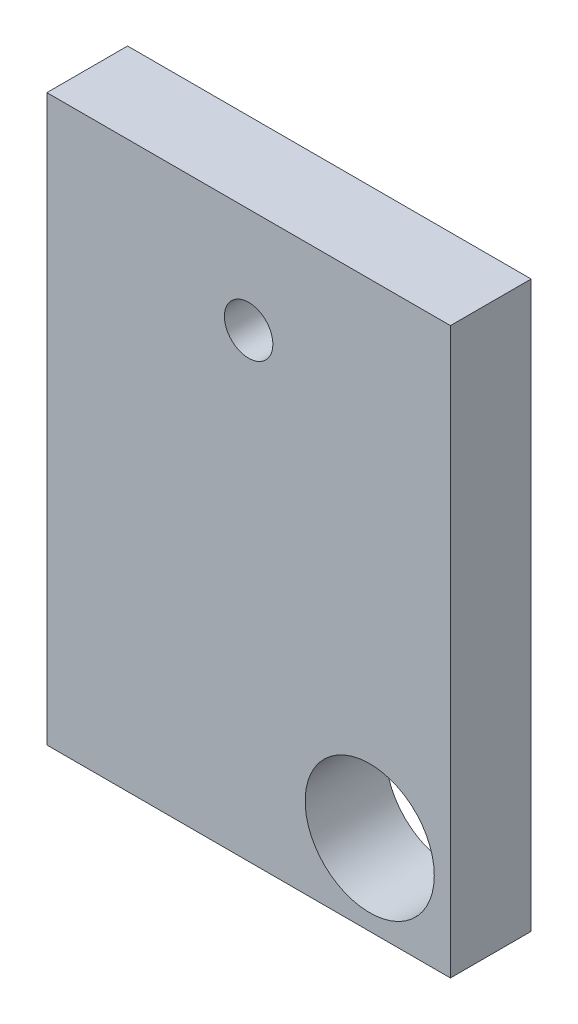
SolidWorks part; units mm, degrees
ref_plane "Front Plane" through (0, 0, 0) normal (0, 0, 1) x (1, 0, 0)
ref_plane "Top Plane" through (0, 0, 0) normal (0, 1, 0) x (1, 0, 0)
ref_plane "Right Plane" through (0, 0, 0) normal (1, 0, 0) x (0, 0, -1)
sketch "Sketch2" plane through (0, 0, 0) normal (0, 0, 1) x (1, 0, 0)
  line L1 (-12.5, -17.5) -> (12.5, -17.5)
  line L2 (-12.5, -17.5) -> (-12.5, 17.5)
  line L3 (-12.5, 17.5) -> (12.5, 17.5)
  line L4 (12.5, -17.5) -> (12.5, 17.5)
  line L5 (-12.5, -17.5) -> (12.5, 17.5) construction
  line L6 (-12.5, 17.5) -> (12.5, -17.5) construction
  point P0 (0, 0)
  dimension "D1" = 25
  dimension "D2" = 35
extrude "Boss-Extrude1" add sketch "Sketch2" along normal blind 5
sketch "Sketch4" plane through (0, 0, 5) normal (0, 0, 1) x (1, 0, 0)
  line L0 (0, -17.5) -> (0, -7.5) construction
  line L1 (-12.5, -17.5) -> (12.5, -17.5) construction
  line L2 (0, -7.5) -> (0, 11) construction
  circle A0 centre (0, 11) radius 1.5
  dimension "D3" = 3
  dimension "D1" = 10
  dimension "D2" = 18.5
extrude "Cut-Extrude1" cut sketch "Sketch4" against normal through all
sketch "Sketch6" plane through (0, 0, 5) normal (0, 0, 1) x (1, 0, 0)
  line L0 (12.5, -17.5) -> (12.5, -7.5) construction
  line L2 (12.5, -17.5) -> (12.5, 17.5) construction
  line L3 (12.5, -12.5) -> (7.5, -12.5) construction
  circle A0 centre (7.5, -12.5) radius 4
  dimension "D2" = 8
  dimension "D1" = 10
  dimension "5" = 5
extrude "Cut-Extrude2" cut sketch "Sketch6" against normal through all
